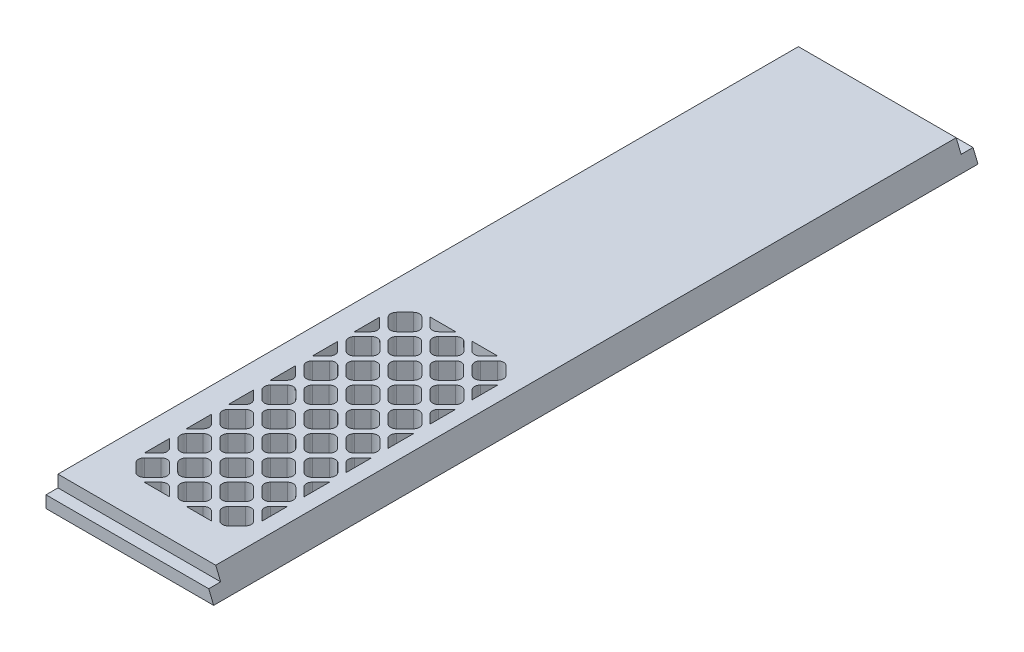
SolidWorks part; units mm, degrees
ref_plane "Front Plane" through (0, 0, 0) normal (0, 0, 1) x (1, 0, 0)
ref_plane "Top Plane" through (0, 0, 0) normal (0, 1, 0) x (1, 0, 0)
ref_plane "Right Plane" through (0, 0, 0) normal (1, 0, 0) x (0, 0, -1)
sketch "Sketch1" plane through (0, 0, 0) normal (0, 0, 1) x (1, 0, 0)
  line L0 (0, 0) -> (0, 12.7)
  line L1 (0, 12.7) -> (83.8935, 12.7)
  line L2 (83.8935, 12.7) -> (89.154, 0)
  line L3 (89.154, 0) -> (0, 0)
  dimension "D1" = 12.7
  dimension "D2" = 67.5
  dimension "D3" = 89.154
extrude "Boss-Extrude1" add sketch "Sketch1" along normal blind 406.4
sketch "Sketch2" plane through (0, 12.7, 0) normal (0, -1, 0) x (1, 0, 0)
  line L0 (0, 406.4) -> (0, 0) construction
  line L1 (0, 6.35) -> (89.154, 6.35)
  line L2 (0, 6.35) -> (0, 0)
  line L3 (0, 0) -> (89.154, 0)
  line L4 (89.154, 6.35) -> (89.154, 0)
  line L5 (89.154, 406.4) -> (89.154, 0) construction
  line L6 (0, 406.4) -> (89.154, 406.4)
  line L7 (0, 406.4) -> (0, 400.05)
  line L8 (0, 400.05) -> (89.154, 400.05)
  line L9 (89.154, 406.4) -> (89.154, 400.05)
  dimension "D1" = 6.35
  dimension "D2" = 6.35
extrude "Cut-Extrude1" cut sketch "Sketch2" along normal blind 6.35
sketch "Sketch3" plane through (0, 0, 0) normal (0, -1, 0) x (1, 0, 0)
  line L0 (15.4898, 374.1011) -> (19.9799, 378.5912)
  line L1 (13.2447, 380.8363) -> (75.9093, 380.8363)
  line L2 (13.2447, 380.8363) -> (13.2447, 228.7637)
  line L3 (13.2447, 228.7637) -> (75.9093, 228.7637)
  line L4 (75.9093, 380.8363) -> (75.9093, 228.7637)
  line L5 (24.4701, 378.5912) -> (28.9602, 374.1011)
  line L6 (28.9602, 369.6109) -> (24.4701, 365.1208)
  line L7 (19.9799, 365.1208) -> (15.4898, 369.6109)
  line L8 (42.3319, 365.1208) -> (37.8418, 369.6109)
  line L9 (37.8418, 374.1011) -> (42.3319, 378.5912)
  line L10 (46.8221, 378.5912) -> (51.3122, 374.1011)
  line L11 (51.3122, 369.6109) -> (46.8221, 365.1208)
  line L12 (64.6839, 365.1208) -> (60.1938, 369.6109)
  line L13 (60.1938, 374.1011) -> (64.6839, 378.5912)
  line L14 (69.1741, 378.5912) -> (73.6642, 374.1011)
  line L15 (73.6642, 369.6109) -> (69.1741, 365.1208)
  line L16 (19.9799, 342.7688) -> (15.4898, 347.2589)
  line L17 (15.4898, 351.7491) -> (19.9799, 356.2392)
  line L18 (24.4701, 356.2392) -> (28.9602, 351.7491)
  line L19 (28.9602, 347.2589) -> (24.4701, 342.7688)
  line L20 (42.3319, 342.7688) -> (37.8418, 347.2589)
  line L21 (37.8418, 351.7491) -> (42.3319, 356.2392)
  line L22 (46.8221, 356.2392) -> (51.3122, 351.7491)
  line L23 (51.3122, 347.2589) -> (46.8221, 342.7688)
  line L24 (64.6839, 342.7688) -> (60.1938, 347.2589)
  line L25 (60.1938, 351.7491) -> (64.6839, 356.2392)
  line L26 (69.1741, 356.2392) -> (73.6642, 351.7491)
  line L27 (73.6642, 347.2589) -> (69.1741, 342.7688)
  line L28 (19.9799, 320.4168) -> (15.4898, 324.9069)
  line L29 (15.4898, 329.3971) -> (19.9799, 333.8872)
  line L30 (24.4701, 333.8872) -> (28.9602, 329.3971)
  line L31 (28.9602, 324.9069) -> (24.4701, 320.4168)
  line L32 (42.3319, 320.4168) -> (37.8418, 324.9069)
  line L33 (37.8418, 329.3971) -> (42.3319, 333.8872)
  line L34 (46.8221, 333.8872) -> (51.3122, 329.3971)
  line L35 (51.3122, 324.9069) -> (46.8221, 320.4168)
  line L36 (64.6839, 320.4168) -> (60.1938, 324.9069)
  line L37 (60.1938, 329.3971) -> (64.6839, 333.8872)
  line L38 (69.1741, 333.8872) -> (73.6642, 329.3971)
  line L39 (73.6642, 324.9069) -> (69.1741, 320.4168)
  line L40 (19.9799, 298.0648) -> (15.4898, 302.5549)
  line L41 (15.4898, 307.0451) -> (19.9799, 311.5352)
  line L42 (24.4701, 311.5352) -> (28.9602, 307.0451)
  line L43 (28.9602, 302.5549) -> (24.4701, 298.0648)
  line L44 (42.3319, 298.0648) -> (37.8418, 302.5549)
  line L45 (37.8418, 307.0451) -> (42.3319, 311.5352)
  line L46 (46.8221, 311.5352) -> (51.3122, 307.0451)
  line L47 (51.3122, 302.5549) -> (46.8221, 298.0648)
  line L48 (64.6839, 298.0648) -> (60.1938, 302.5549)
  line L49 (60.1938, 307.0451) -> (64.6839, 311.5352)
  line L50 (69.1741, 311.5352) -> (73.6642, 307.0451)
  line L51 (73.6642, 302.5549) -> (69.1741, 298.0648)
  line L52 (19.9799, 275.7128) -> (15.4898, 280.2029)
  line L53 (15.4898, 284.6931) -> (19.9799, 289.1832)
  line L54 (24.4701, 289.1832) -> (28.9602, 284.6931)
  line L55 (28.9602, 280.2029) -> (24.4701, 275.7128)
  line L56 (42.3319, 275.7128) -> (37.8418, 280.2029)
  line L57 (37.8418, 284.6931) -> (42.3319, 289.1832)
  line L58 (46.8221, 289.1832) -> (51.3122, 284.6931)
  line L59 (51.3122, 280.2029) -> (46.8221, 275.7128)
  line L60 (64.6839, 275.7128) -> (60.1938, 280.2029)
  line L61 (60.1938, 284.6931) -> (64.6839, 289.1832)
  line L62 (69.1741, 289.1832) -> (73.6642, 284.6931)
  line L63 (73.6642, 280.2029) -> (69.1741, 275.7128)
  line L64 (19.9799, 253.3608) -> (15.4898, 257.8509)
  line L65 (15.4898, 262.3411) -> (19.9799, 266.8312)
  line L66 (24.4701, 266.8312) -> (28.9602, 262.3411)
  line L67 (28.9602, 257.8509) -> (24.4701, 253.3608)
  line L68 (42.3319, 253.3608) -> (37.8418, 257.8509)
  line L69 (37.8418, 262.3411) -> (42.3319, 266.8312)
  line L70 (46.8221, 266.8312) -> (51.3122, 262.3411)
  line L71 (51.3122, 257.8509) -> (46.8221, 253.3608)
  line L72 (64.6839, 253.3608) -> (60.1938, 257.8509)
  line L73 (60.1938, 262.3411) -> (64.6839, 266.8312)
  line L74 (69.1741, 266.8312) -> (73.6642, 262.3411)
  line L75 (73.6642, 257.8509) -> (69.1741, 253.3608)
  line L76 (19.9799, 231.0088) -> (15.4898, 235.4989)
  line L77 (15.4898, 239.9891) -> (19.9799, 244.4792)
  line L78 (24.4701, 244.4792) -> (28.9602, 239.9891)
  line L79 (28.9602, 235.4989) -> (24.4701, 231.0088)
  line L80 (42.3319, 231.0088) -> (37.8418, 235.4989)
  line L81 (37.8418, 239.9891) -> (42.3319, 244.4792)
  line L82 (46.8221, 244.4792) -> (51.3122, 239.9891)
  line L83 (51.3122, 235.4989) -> (46.8221, 231.0088)
  line L84 (64.6839, 231.0088) -> (60.1938, 235.4989)
  line L85 (60.1938, 239.9891) -> (64.6839, 244.4792)
  line L86 (69.1741, 244.4792) -> (73.6642, 239.9891)
  line L87 (73.6642, 235.4989) -> (69.1741, 231.0088)
  line L91 (0, 400.05) -> (89.154, 400.05) construction
  line L92 (13.2447, 376.3461) -> (17.7349, 380.8363)
  line L98 (35.5967, 376.3461) -> (40.0869, 380.8363)
  line L99 (31.1066, 376.3461) -> (26.6165, 380.8363)
  line L102 (57.9487, 376.3461) -> (62.4389, 380.8363)
  line L103 (53.4586, 376.3461) -> (48.9685, 380.8363)
  line L107 (75.8106, 376.3461) -> (71.3205, 380.8363)
  line L108 (26.6165, 362.9744) -> (31.1066, 367.4645)
  line L109 (40.0869, 362.9744) -> (35.5967, 367.4645)
  line L110 (35.5967, 353.9941) -> (40.0869, 358.4843)
  line L111 (31.1066, 353.9941) -> (26.6165, 358.4843)
  line L112 (48.9685, 362.9744) -> (53.4586, 367.4645)
  line L113 (62.4389, 362.9744) -> (57.9487, 367.4645)
  line L114 (57.9487, 353.9941) -> (62.4389, 358.4843)
  line L115 (53.4586, 353.9941) -> (48.9685, 358.4843)
  line L116 (71.3205, 362.9744) -> (75.8106, 367.4645)
  line L119 (75.8106, 353.9941) -> (71.3205, 358.4843)
  line L120 (26.6165, 340.6224) -> (31.1066, 345.1125)
  line L121 (40.0869, 340.6224) -> (35.5967, 345.1125)
  line L122 (35.5967, 331.6421) -> (40.0869, 336.1323)
  line L123 (31.1066, 331.6421) -> (26.6165, 336.1323)
  line L124 (48.9685, 340.6224) -> (53.4586, 345.1125)
  line L125 (62.4389, 340.6224) -> (57.9487, 345.1125)
  line L126 (57.9487, 331.6421) -> (62.4389, 336.1323)
  line L127 (53.4586, 331.6421) -> (48.9685, 336.1323)
  line L128 (71.3205, 340.6224) -> (75.8106, 345.1125)
  line L131 (75.8106, 331.6421) -> (71.3205, 336.1323)
  line L132 (26.6165, 318.2704) -> (31.1066, 322.7605)
  line L133 (40.0869, 318.2704) -> (35.5967, 322.7605)
  line L134 (35.5967, 309.2901) -> (40.0869, 313.7803)
  line L135 (31.1066, 309.2901) -> (26.6165, 313.7803)
  line L136 (48.9685, 318.2704) -> (53.4586, 322.7605)
  line L137 (62.4389, 318.2704) -> (57.9487, 322.7605)
  line L138 (57.9487, 309.2901) -> (62.4389, 313.7803)
  line L139 (53.4586, 309.2901) -> (48.9685, 313.7803)
  line L140 (71.3205, 318.2704) -> (75.8106, 322.7605)
  line L143 (75.8106, 309.2901) -> (71.3205, 313.7803)
  line L144 (26.6165, 295.9184) -> (31.1066, 300.4085)
  line L145 (40.0869, 295.9184) -> (35.5967, 300.4085)
  line L146 (35.5967, 286.9381) -> (40.0869, 291.4283)
  line L147 (31.1066, 286.9381) -> (26.6165, 291.4283)
  line L148 (48.9685, 295.9184) -> (53.4586, 300.4085)
  line L149 (62.4389, 295.9184) -> (57.9487, 300.4085)
  line L150 (57.9487, 286.9381) -> (62.4389, 291.4283)
  line L151 (53.4586, 286.9381) -> (48.9685, 291.4283)
  line L152 (71.3205, 295.9184) -> (75.8106, 300.4085)
  line L155 (75.8106, 286.9381) -> (71.3205, 291.4283)
  line L156 (26.6165, 273.5664) -> (31.1066, 278.0565)
  line L157 (40.0869, 273.5664) -> (35.5967, 278.0565)
  line L158 (35.5967, 264.5861) -> (40.0869, 269.0763)
  line L159 (31.1066, 264.5861) -> (26.6165, 269.0763)
  line L160 (48.9685, 273.5664) -> (53.4586, 278.0565)
  line L161 (62.4389, 273.5664) -> (57.9487, 278.0565)
  line L162 (57.9487, 264.5861) -> (62.4389, 269.0763)
  line L163 (53.4586, 264.5861) -> (48.9685, 269.0763)
  line L164 (71.3205, 273.5664) -> (75.8106, 278.0565)
  line L167 (75.8106, 264.5861) -> (71.3205, 269.0763)
  line L168 (26.6165, 251.2144) -> (31.1066, 255.7045)
  line L169 (40.0869, 251.2144) -> (35.5967, 255.7045)
  line L170 (35.5967, 242.2341) -> (40.0869, 246.7243)
  line L171 (31.1066, 242.2341) -> (26.6165, 246.7243)
  line L172 (48.9685, 251.2144) -> (53.4586, 255.7045)
  line L173 (62.4389, 251.2144) -> (57.9487, 255.7045)
  line L174 (57.9487, 242.2341) -> (62.4389, 246.7243)
  line L175 (53.4586, 242.2341) -> (48.9685, 246.7243)
  line L176 (71.3205, 251.2144) -> (75.8106, 255.7045)
  line L179 (75.8106, 242.2341) -> (71.3205, 246.7243)
  line L180 (26.6165, 228.8624) -> (31.1066, 233.3525)
  line L181 (40.0869, 228.8624) -> (35.5967, 233.3525)
  line L184 (48.9685, 228.8624) -> (53.4586, 233.3525)
  line L185 (62.4389, 228.8624) -> (57.9487, 233.3525)
  line L188 (71.3205, 228.8624) -> (75.8106, 233.3525)
  line L193 (17.7349, 362.9744) -> (13.2447, 367.4645)
  line L194 (13.2447, 353.9941) -> (17.7349, 358.4843)
  line L197 (17.7349, 340.6224) -> (13.2447, 345.1125)
  line L198 (13.2447, 331.6421) -> (17.7349, 336.1323)
  line L201 (17.7349, 318.2704) -> (13.2447, 322.7605)
  line L202 (13.2447, 309.2901) -> (17.7349, 313.7803)
  line L205 (17.7349, 295.9184) -> (13.2447, 300.4085)
  line L206 (13.2447, 286.9381) -> (17.7349, 291.4283)
  line L209 (17.7349, 273.5664) -> (13.2447, 278.0565)
  line L210 (13.2447, 264.5861) -> (17.7349, 269.0763)
  line L213 (17.7349, 251.2144) -> (13.2447, 255.7045)
  line L214 (13.2447, 242.2341) -> (17.7349, 246.7243)
  line L217 (17.7349, 228.8624) -> (13.2447, 233.3525)
  line L220 (80.3007, 376.3461) -> (84.7909, 380.8363) [skipped]
  line L221 (80.3007, 353.9941) -> (84.7909, 358.4843) [skipped]
  line L222 (80.3007, 331.6421) -> (84.7909, 336.1323) [skipped]
  line L223 (80.3007, 309.2901) -> (84.7909, 313.7803) [skipped]
  line L224 (80.3007, 286.9381) -> (84.7909, 291.4283) [skipped]
  line L225 (80.3007, 264.5861) -> (84.7909, 269.0763) [skipped]
  line L226 (80.3007, 242.2341) -> (84.7909, 246.7243) [skipped]
  line L227 (80.3007, 219.8821) -> (84.7909, 224.3723) [skipped]
  line L228 (57.9487, 219.8821) -> (62.4389, 224.3723) [skipped]
  line L229 (35.5967, 219.8821) -> (40.0869, 224.3723) [skipped]
  line L230 (13.2447, 219.8821) -> (17.7349, 224.3723) [skipped]
  arc A0 (24.4701, 365.1208) -> (19.9799, 365.1208) centre (22.225, 367.3659) cw
  arc A1 (28.9602, 374.1011) -> (28.9602, 369.6109) centre (26.7151, 371.856) cw
  arc A2 (15.4898, 374.1011) -> (15.4898, 369.6109) centre (17.7349, 371.856) ccw
  arc A3 (19.9799, 378.5912) -> (24.4701, 378.5912) centre (22.225, 376.3461) cw
  arc A4 (37.8418, 374.1011) -> (37.8418, 369.6109) centre (40.0869, 371.856) ccw
  arc A5 (46.8221, 365.1208) -> (42.3319, 365.1208) centre (44.577, 367.3659) cw
  arc A6 (42.3319, 378.5912) -> (46.8221, 378.5912) centre (44.577, 376.3461) cw
  arc A7 (51.3122, 374.1011) -> (51.3122, 369.6109) centre (49.0671, 371.856) cw
  arc A8 (60.1938, 374.1011) -> (60.1938, 369.6109) centre (62.4389, 371.856) ccw
  arc A9 (69.1741, 365.1208) -> (64.6839, 365.1208) centre (66.929, 367.3659) cw
  arc A10 (64.6839, 378.5912) -> (69.1741, 378.5912) centre (66.929, 376.3461) cw
  arc A11 (73.6642, 374.1011) -> (73.6642, 369.6109) centre (71.4191, 371.856) cw
  arc A12 (15.4898, 351.7491) -> (15.4898, 347.2589) centre (17.7349, 349.504) ccw
  arc A13 (24.4701, 342.7688) -> (19.9799, 342.7688) centre (22.225, 345.0139) cw
  arc A14 (19.9799, 356.2392) -> (24.4701, 356.2392) centre (22.225, 353.9941) cw
  arc A15 (28.9602, 351.7491) -> (28.9602, 347.2589) centre (26.7151, 349.504) cw
  arc A16 (37.8418, 351.7491) -> (37.8418, 347.2589) centre (40.0869, 349.504) ccw
  arc A17 (42.3319, 356.2392) -> (46.8221, 356.2392) centre (44.577, 353.9941) cw
  arc A18 (51.3122, 351.7491) -> (51.3122, 347.2589) centre (49.0671, 349.504) cw
  arc A19 (46.8221, 342.7688) -> (42.3319, 342.7688) centre (44.577, 345.0139) cw
  arc A20 (60.1938, 351.7491) -> (60.1938, 347.2589) centre (62.4389, 349.504) ccw
  arc A21 (64.6839, 356.2392) -> (69.1741, 356.2392) centre (66.929, 353.9941) cw
  arc A22 (73.6642, 351.7491) -> (73.6642, 347.2589) centre (71.4191, 349.504) cw
  arc A23 (69.1741, 342.7688) -> (64.6839, 342.7688) centre (66.929, 345.0139) cw
  arc A24 (15.4898, 329.3971) -> (15.4898, 324.9069) centre (17.7349, 327.152) ccw
  arc A25 (24.4701, 320.4168) -> (19.9799, 320.4168) centre (22.225, 322.6619) cw
  arc A26 (19.9799, 333.8872) -> (24.4701, 333.8872) centre (22.225, 331.6421) cw
  arc A27 (28.9602, 329.3971) -> (28.9602, 324.9069) centre (26.7151, 327.152) cw
  arc A28 (37.8418, 329.3971) -> (37.8418, 324.9069) centre (40.0869, 327.152) ccw
  arc A29 (42.3319, 333.8872) -> (46.8221, 333.8872) centre (44.577, 331.6421) cw
  arc A30 (51.3122, 329.3971) -> (51.3122, 324.9069) centre (49.0671, 327.152) cw
  arc A31 (46.8221, 320.4168) -> (42.3319, 320.4168) centre (44.577, 322.6619) cw
  arc A32 (60.1938, 329.3971) -> (60.1938, 324.9069) centre (62.4389, 327.152) ccw
  arc A33 (64.6839, 333.8872) -> (69.1741, 333.8872) centre (66.929, 331.6421) cw
  arc A34 (73.6642, 329.3971) -> (73.6642, 324.9069) centre (71.4191, 327.152) cw
  arc A35 (69.1741, 320.4168) -> (64.6839, 320.4168) centre (66.929, 322.6619) cw
  arc A36 (15.4898, 307.0451) -> (15.4898, 302.5549) centre (17.7349, 304.8) ccw
  arc A37 (24.4701, 298.0648) -> (19.9799, 298.0648) centre (22.225, 300.3099) cw
  arc A38 (19.9799, 311.5352) -> (24.4701, 311.5352) centre (22.225, 309.2901) cw
  arc A39 (28.9602, 307.0451) -> (28.9602, 302.5549) centre (26.7151, 304.8) cw
  arc A40 (37.8418, 307.0451) -> (37.8418, 302.5549) centre (40.0869, 304.8) ccw
  arc A41 (42.3319, 311.5352) -> (46.8221, 311.5352) centre (44.577, 309.2901) cw
  arc A42 (51.3122, 307.0451) -> (51.3122, 302.5549) centre (49.0671, 304.8) cw
  arc A43 (46.8221, 298.0648) -> (42.3319, 298.0648) centre (44.577, 300.3099) cw
  arc A44 (60.1938, 307.0451) -> (60.1938, 302.5549) centre (62.4389, 304.8) ccw
  arc A45 (64.6839, 311.5352) -> (69.1741, 311.5352) centre (66.929, 309.2901) cw
  arc A46 (73.6642, 307.0451) -> (73.6642, 302.5549) centre (71.4191, 304.8) cw
  arc A47 (69.1741, 298.0648) -> (64.6839, 298.0648) centre (66.929, 300.3099) cw
  arc A48 (15.4898, 284.6931) -> (15.4898, 280.2029) centre (17.7349, 282.448) ccw
  arc A49 (24.4701, 275.7128) -> (19.9799, 275.7128) centre (22.225, 277.9579) cw
  arc A50 (19.9799, 289.1832) -> (24.4701, 289.1832) centre (22.225, 286.9381) cw
  arc A51 (28.9602, 284.6931) -> (28.9602, 280.2029) centre (26.7151, 282.448) cw
  arc A52 (37.8418, 284.6931) -> (37.8418, 280.2029) centre (40.0869, 282.448) ccw
  arc A53 (42.3319, 289.1832) -> (46.8221, 289.1832) centre (44.577, 286.9381) cw
  arc A54 (51.3122, 284.6931) -> (51.3122, 280.2029) centre (49.0671, 282.448) cw
  arc A55 (46.8221, 275.7128) -> (42.3319, 275.7128) centre (44.577, 277.9579) cw
  arc A56 (60.1938, 284.6931) -> (60.1938, 280.2029) centre (62.4389, 282.448) ccw
  arc A57 (64.6839, 289.1832) -> (69.1741, 289.1832) centre (66.929, 286.9381) cw
  arc A58 (73.6642, 284.6931) -> (73.6642, 280.2029) centre (71.4191, 282.448) cw
  arc A59 (69.1741, 275.7128) -> (64.6839, 275.7128) centre (66.929, 277.9579) cw
  arc A60 (15.4898, 262.3411) -> (15.4898, 257.8509) centre (17.7349, 260.096) ccw
  arc A61 (24.4701, 253.3608) -> (19.9799, 253.3608) centre (22.225, 255.6059) cw
  arc A62 (19.9799, 266.8312) -> (24.4701, 266.8312) centre (22.225, 264.5861) cw
  arc A63 (28.9602, 262.3411) -> (28.9602, 257.8509) centre (26.7151, 260.096) cw
  arc A64 (37.8418, 262.3411) -> (37.8418, 257.8509) centre (40.0869, 260.096) ccw
  arc A65 (42.3319, 266.8312) -> (46.8221, 266.8312) centre (44.577, 264.5861) cw
  arc A66 (51.3122, 262.3411) -> (51.3122, 257.8509) centre (49.0671, 260.096) cw
  arc A67 (46.8221, 253.3608) -> (42.3319, 253.3608) centre (44.577, 255.6059) cw
  arc A68 (60.1938, 262.3411) -> (60.1938, 257.8509) centre (62.4389, 260.096) ccw
  arc A69 (64.6839, 266.8312) -> (69.1741, 266.8312) centre (66.929, 264.5861) cw
  arc A70 (73.6642, 262.3411) -> (73.6642, 257.8509) centre (71.4191, 260.096) cw
  arc A71 (69.1741, 253.3608) -> (64.6839, 253.3608) centre (66.929, 255.6059) cw
  arc A72 (15.4898, 239.9891) -> (15.4898, 235.4989) centre (17.7349, 237.744) ccw
  arc A73 (24.4701, 231.0088) -> (19.9799, 231.0088) centre (22.225, 233.2539) cw
  arc A74 (19.9799, 244.4792) -> (24.4701, 244.4792) centre (22.225, 242.2341) cw
  arc A75 (28.9602, 239.9891) -> (28.9602, 235.4989) centre (26.7151, 237.744) cw
  arc A76 (37.8418, 239.9891) -> (37.8418, 235.4989) centre (40.0869, 237.744) ccw
  arc A77 (42.3319, 244.4792) -> (46.8221, 244.4792) centre (44.577, 242.2341) cw
  arc A78 (51.3122, 239.9891) -> (51.3122, 235.4989) centre (49.0671, 237.744) cw
  arc A79 (46.8221, 231.0088) -> (42.3319, 231.0088) centre (44.577, 233.2539) cw
  arc A80 (60.1938, 239.9891) -> (60.1938, 235.4989) centre (62.4389, 237.744) ccw
  arc A81 (64.6839, 244.4792) -> (69.1741, 244.4792) centre (66.929, 242.2341) cw
  arc A82 (73.6642, 239.9891) -> (73.6642, 235.4989) centre (71.4191, 237.744) cw
  arc A83 (69.1741, 231.0088) -> (64.6839, 231.0088) centre (66.929, 233.2539) cw
  arc A91 (35.5967, 376.3461) -> (31.1066, 376.3461) centre (33.3517, 378.5912) cw
  arc A95 (57.9487, 376.3461) -> (53.4586, 376.3461) centre (55.7037, 378.5912) cw
  arc A99 (75.9093, 376.2516) -> (75.8106, 376.3461) centre (78.0557, 378.5912) cw
  arc A100 (35.5967, 367.4645) -> (31.1066, 367.4645) centre (33.3517, 365.2194) ccw
  arc A101 (26.6165, 358.4843) -> (26.6165, 362.9744) centre (28.8616, 360.7293) cw
  arc A102 (40.0869, 358.4843) -> (40.0869, 362.9744) centre (37.8418, 360.7293) ccw
  arc A103 (35.5967, 353.9941) -> (31.1066, 353.9941) centre (33.3517, 356.2392) cw
  arc A104 (57.9487, 367.4645) -> (53.4586, 367.4645) centre (55.7037, 365.2194) ccw
  arc A105 (48.9685, 358.4843) -> (48.9685, 362.9744) centre (51.2136, 360.7293) cw
  arc A106 (62.4389, 358.4843) -> (62.4389, 362.9744) centre (60.1938, 360.7293) ccw
  arc A107 (57.9487, 353.9941) -> (53.4586, 353.9941) centre (55.7037, 356.2392) cw
  arc A108 (75.9093, 367.559) -> (75.8106, 367.4645) centre (78.0557, 365.2194) ccw
  arc A109 (71.3205, 358.4843) -> (71.3205, 362.9744) centre (73.5656, 360.7293) cw
  arc A111 (75.9093, 353.8996) -> (75.8106, 353.9941) centre (78.0557, 356.2392) cw
  arc A112 (35.5967, 345.1125) -> (31.1066, 345.1125) centre (33.3517, 342.8674) ccw
  arc A113 (26.6165, 336.1323) -> (26.6165, 340.6224) centre (28.8616, 338.3773) cw
  arc A114 (40.0869, 336.1323) -> (40.0869, 340.6224) centre (37.8418, 338.3773) ccw
  arc A115 (35.5967, 331.6421) -> (31.1066, 331.6421) centre (33.3517, 333.8872) cw
  arc A116 (57.9487, 345.1125) -> (53.4586, 345.1125) centre (55.7037, 342.8674) ccw
  arc A117 (48.9685, 336.1323) -> (48.9685, 340.6224) centre (51.2136, 338.3773) cw
  arc A118 (62.4389, 336.1323) -> (62.4389, 340.6224) centre (60.1938, 338.3773) ccw
  arc A119 (57.9487, 331.6421) -> (53.4586, 331.6421) centre (55.7037, 333.8872) cw
  arc A120 (75.9093, 345.207) -> (75.8106, 345.1125) centre (78.0557, 342.8674) ccw
  arc A121 (71.3205, 336.1323) -> (71.3205, 340.6224) centre (73.5656, 338.3773) cw
  arc A123 (75.9093, 331.5476) -> (75.8106, 331.6421) centre (78.0557, 333.8872) cw
  arc A124 (35.5967, 322.7605) -> (31.1066, 322.7605) centre (33.3517, 320.5154) ccw
  arc A125 (26.6165, 313.7803) -> (26.6165, 318.2704) centre (28.8616, 316.0253) cw
  arc A126 (40.0869, 313.7803) -> (40.0869, 318.2704) centre (37.8418, 316.0253) ccw
  arc A127 (35.5967, 309.2901) -> (31.1066, 309.2901) centre (33.3517, 311.5352) cw
  arc A128 (57.9487, 322.7605) -> (53.4586, 322.7605) centre (55.7037, 320.5154) ccw
  arc A129 (48.9685, 313.7803) -> (48.9685, 318.2704) centre (51.2136, 316.0253) cw
  arc A130 (62.4389, 313.7803) -> (62.4389, 318.2704) centre (60.1938, 316.0253) ccw
  arc A131 (57.9487, 309.2901) -> (53.4586, 309.2901) centre (55.7037, 311.5352) cw
  arc A132 (75.9093, 322.855) -> (75.8106, 322.7605) centre (78.0557, 320.5154) ccw
  arc A133 (71.3205, 313.7803) -> (71.3205, 318.2704) centre (73.5656, 316.0253) cw
  arc A135 (75.9093, 309.1956) -> (75.8106, 309.2901) centre (78.0557, 311.5352) cw
  arc A136 (35.5967, 300.4085) -> (31.1066, 300.4085) centre (33.3517, 298.1634) ccw
  arc A137 (26.6165, 291.4283) -> (26.6165, 295.9184) centre (28.8616, 293.6733) cw
  arc A138 (40.0869, 291.4283) -> (40.0869, 295.9184) centre (37.8418, 293.6733) ccw
  arc A139 (35.5967, 286.9381) -> (31.1066, 286.9381) centre (33.3517, 289.1832) cw
  arc A140 (57.9487, 300.4085) -> (53.4586, 300.4085) centre (55.7037, 298.1634) ccw
  arc A141 (48.9685, 291.4283) -> (48.9685, 295.9184) centre (51.2136, 293.6733) cw
  arc A142 (62.4389, 291.4283) -> (62.4389, 295.9184) centre (60.1938, 293.6733) ccw
  arc A143 (57.9487, 286.9381) -> (53.4586, 286.9381) centre (55.7037, 289.1832) cw
  arc A144 (75.9093, 300.503) -> (75.8106, 300.4085) centre (78.0557, 298.1634) ccw
  arc A145 (71.3205, 291.4283) -> (71.3205, 295.9184) centre (73.5656, 293.6733) cw
  arc A147 (75.9093, 286.8436) -> (75.8106, 286.9381) centre (78.0557, 289.1832) cw
  arc A148 (35.5967, 278.0565) -> (31.1066, 278.0565) centre (33.3517, 275.8114) ccw
  arc A149 (26.6165, 269.0763) -> (26.6165, 273.5664) centre (28.8616, 271.3213) cw
  arc A150 (40.0869, 269.0763) -> (40.0869, 273.5664) centre (37.8418, 271.3213) ccw
  arc A151 (35.5967, 264.5861) -> (31.1066, 264.5861) centre (33.3517, 266.8312) cw
  arc A152 (57.9487, 278.0565) -> (53.4586, 278.0565) centre (55.7037, 275.8114) ccw
  arc A153 (48.9685, 269.0763) -> (48.9685, 273.5664) centre (51.2136, 271.3213) cw
  arc A154 (62.4389, 269.0763) -> (62.4389, 273.5664) centre (60.1938, 271.3213) ccw
  arc A155 (57.9487, 264.5861) -> (53.4586, 264.5861) centre (55.7037, 266.8312) cw
  arc A156 (75.9093, 278.151) -> (75.8106, 278.0565) centre (78.0557, 275.8114) ccw
  arc A157 (71.3205, 269.0763) -> (71.3205, 273.5664) centre (73.5656, 271.3213) cw
  arc A159 (75.9093, 264.4916) -> (75.8106, 264.5861) centre (78.0557, 266.8312) cw
  arc A160 (35.5967, 255.7045) -> (31.1066, 255.7045) centre (33.3517, 253.4594) ccw
  arc A161 (26.6165, 246.7243) -> (26.6165, 251.2144) centre (28.8616, 248.9693) cw
  arc A162 (40.0869, 246.7243) -> (40.0869, 251.2144) centre (37.8418, 248.9693) ccw
  arc A163 (35.5967, 242.2341) -> (31.1066, 242.2341) centre (33.3517, 244.4792) cw
  arc A164 (57.9487, 255.7045) -> (53.4586, 255.7045) centre (55.7037, 253.4594) ccw
  arc A165 (48.9685, 246.7243) -> (48.9685, 251.2144) centre (51.2136, 248.9693) cw
  arc A166 (62.4389, 246.7243) -> (62.4389, 251.2144) centre (60.1938, 248.9693) ccw
  arc A167 (57.9487, 242.2341) -> (53.4586, 242.2341) centre (55.7037, 244.4792) cw
  arc A168 (75.9093, 255.799) -> (75.8106, 255.7045) centre (78.0557, 253.4594) ccw
  arc A169 (71.3205, 246.7243) -> (71.3205, 251.2144) centre (73.5656, 248.9693) cw
  arc A171 (75.9093, 242.1396) -> (75.8106, 242.2341) centre (78.0557, 244.4792) cw
  arc A172 (35.5967, 233.3525) -> (31.1066, 233.3525) centre (33.3517, 231.1074) ccw
  arc A173 (26.522, 228.7637) -> (26.6165, 228.8624) centre (28.8616, 226.6173) cw
  arc A174 (40.1814, 228.7637) -> (40.0869, 228.8624) centre (37.8418, 226.6173) ccw
  arc A176 (57.9487, 233.3525) -> (53.4586, 233.3525) centre (55.7037, 231.1074) ccw
  arc A177 (48.874, 228.7637) -> (48.9685, 228.8624) centre (51.2136, 226.6173) cw
  arc A178 (62.5334, 228.7637) -> (62.4389, 228.8624) centre (60.1938, 226.6173) ccw
  arc A180 (75.9093, 233.447) -> (75.8106, 233.3525) centre (78.0557, 231.1074) ccw
  arc A181 (71.226, 228.7637) -> (71.3205, 228.8624) centre (73.5656, 226.6173) cw
  arc A186 (17.7349, 358.4843) -> (17.7349, 362.9744) centre (15.4898, 360.7293) ccw
  arc A190 (17.7349, 336.1323) -> (17.7349, 340.6224) centre (15.4898, 338.3773) ccw
  arc A194 (17.7349, 313.7803) -> (17.7349, 318.2704) centre (15.4898, 316.0253) ccw
  arc A198 (17.7349, 291.4283) -> (17.7349, 295.9184) centre (15.4898, 293.6733) ccw
  arc A202 (17.7349, 269.0763) -> (17.7349, 273.5664) centre (15.4898, 271.3213) ccw
  arc A206 (17.7349, 246.7243) -> (17.7349, 251.2144) centre (15.4898, 248.9693) ccw
  arc A210 (17.8294, 228.7637) -> (17.7349, 228.8624) centre (15.4898, 226.6173) ccw
  point P11 (22.225, 362.8757)
  point P16 (13.2447, 371.856)
  point P19 (22.225, 380.8363)
  point P44 (44.577, 380.8363)
  point P45 (13.2447, 304.8)
  point P262 (0, 0)
  point P263 (0, 0)
  point P272 (44.577, 400.05)
  point P281 (10.9997, 374.1011)
  point P284 (2.0194, 383.0813)
  point P287 (10.9997, 392.0616)
  point P306 (0, 0)
  dimension "D4" = 3.175
  dimension "D1" = 12.7
  dimension "D2" = 45
  dimension "D3" = 12.7
  dimension "D8" = 12.7
  dimension "D9" = 12.7
  dimension "D10" = 3.175
  dimension "D5" = 3
  dimension "D7" = 7
extrude "Cut-Extrude3" cut sketch "Sketch3" against normal through all contours A3 L0 A2 L7 A0 L6 A1 L5 | A7 L10 A6 L9 A4 L8 A5 L11 | A11 L14 A10 L13 A8 L12 A9 L15 | A91 L98 L1 L99 | L194 A186 L193 L2 | A103 L110 A102 L109 A100 L108 A101 L111 | A107 L114 A106 L113 A104 L112 A105 L115 | A111 L4 A108 L116 A109 L119 | A15 L18 A14 L17 A12 L16 A13 L19 | A19 L23 A18 L22 A17 L21 A16 L20 | A23 L27 A22 L26 A21 L25 A20 L24 | A123 L4 A120 L128 A121 L131 | A119 L126 A118 L125 A116 L124 A117 L127 | A115 L122 A114 L121 A112 L120 A113 L123 | L198 A190 L197 L2 | A27 L30 A26 L29 A24 L28 A25 L31 | A31 L35 A30 L34 A29 L33 A28 L32 | A35 L39 A34 L38 A33 L37 A32 L36 | A131 L138 A130 L137 A128 L136 A129 L139 | A135 L4 A132 L140 A133 L143 | A95 L102 L1 L103 | A127 L134 A126 L133 A124 L132 A125 L135 | L202 A194 L201 L2 | A39 L42 A38 L41 A36 L40 A37 L43 | A43 L47 A42 L46 A41 L45 A40 L44 | A47 L51 A46 L50 A45 L49 A44 L48 | L206 A198 L205 L2 | A51 L54 A50 L53 A48 L52 A49 L55 | A139 L146 A138 L145 A136 L144 A137 L147 | A55 L59 A54 L58 A53 L57 A52 L56 | A143 L150 A142 L149 A140 L148 A141 L151 | A147 L4 A144 L152 A145 L155 | A59 L63 A58 L62 A57 L61 A56 L60 | L210 A202 L209 L2 | A151 L158 A150 L157 A148 L156 A149 L159 | A155 L162 A154 L161 A152 L160 A153 L163 | A159 L4 A156 L164 A157 L167 | A71 L75 A70 L74 A69 L73 A68 L72 | A67 L71 A66 L70 A65 L69 A64 L68 | A63 L66 A62 L65 A60 L64 A61 L67 | L214 A206 L213 L2 | A75 L78 A74 L77 A72 L76 A73 L79 | A163 L170 A162 L169 A160 L168 A161 L171 | L3 A174 L181 A172 L180 A173 | A79 L83 A78 L82 A77 L81 A76 L80 | A167 L174 A166 L173 A164 L172 A165 L175 | A171 L4 A168 L176 A169 L179 | A83 L87 A82 L86 A81 L85 A80 L84 | L3 A178 L185 A176 L184 A177 region at (22.225, 0, 371.856) region at (33.3517, 0, 378.7658) region at (15.3152, 0, 360.7293) region at (55.7037, 0, 378.7658) region at (15.3152, 0, 338.3773) region at (15.3152, 0, 316.0253) region at (15.3152, 0, 293.6733) region at (73.8039, 0, 360.7293) region at (15.3152, 0, 271.3213) region at (73.8039, 0, 338.3773) region at (15.3152, 0, 248.9693) region at (73.8039, 0, 316.0253) region at (73.8039, 0, 293.6733) region at (73.8039, 0, 271.3213) region at (33.3517, 0, 230.8691) region at (73.8039, 0, 248.9693) region at (55.7037, 0, 230.8691) region at (44.577, 0, 371.856) region at (66.929, 0, 371.856) region at (22.225, 0, 349.504) region at (44.577, 0, 349.504) region at (66.929, 0, 349.504) region at (22.225, 0, 327.152) region at (44.577, 0, 327.152) region at (66.929, 0, 327.152) region at (22.225, 0, 304.8) region at (44.577, 0, 304.8) region at (66.929, 0, 304.8) region at (22.225, 0, 282.448) region at (44.577, 0, 282.448) region at (66.929, 0, 282.448) region at (22.225, 0, 260.096) region at (44.577, 0, 260.096) region at (66.929, 0, 260.096) region at (22.225, 0, 237.744) region at (44.577, 0, 237.744) region at (66.929, 0, 237.744) region at (33.3517, 0, 360.7293) region at (55.7037, 0, 360.7293) region at (33.3517, 0, 338.3773) region at (55.7037, 0, 338.3773) region at (33.3517, 0, 316.0253) region at (55.7037, 0, 316.0253) region at (33.3517, 0, 293.6733) region at (55.7037, 0, 293.6733) region at (33.3517, 0, 271.3213) region at (55.7037, 0, 271.3213) region at (33.3517, 0, 248.9693) region at (55.7037, 0, 248.9693)
